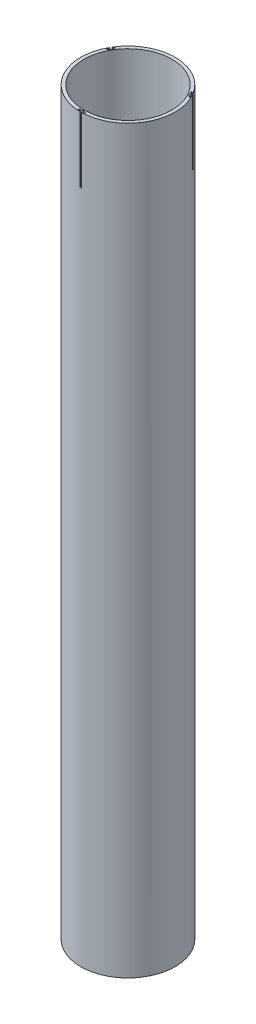
SolidWorks part; units mm, degrees
ref_plane "Front Plane" through (0, 0, 0) normal (0, 0, 1) x (1, 0, 0)
ref_plane "Top Plane" through (0, 0, 0) normal (0, 1, 0) x (1, 0, 0)
ref_plane "Right Plane" through (0, 0, 0) normal (1, 0, 0) x (0, 0, -1)
sketch "Sketch1" plane through (0, 0, 0) normal (0, 1, 0) x (1, 0, 0)
  circle A0 centre (0, 0) radius 57.5
  dimension "D1" = 115
extrude "Boss-Extrude1" add sketch "Sketch1" along normal mid plane 900
ref_plane "Plane1" through (0, 370, 0) normal (0, 1, 0) x (1, 0, 0)
ref_plane "Plane2" through (0, 450, 0) normal (0, 1, 0) x (1, 0, 0)
shell "Shell1" thickness 4 removed face at (0, 450, 57.5) removed face at (0, -450, 57.5)
sketch "Sketch2" plane through (0, 450, 0) normal (0, 1, 0) x (1, 0, 0)
  line L0 (0, 64.7023) -> (0, -68.4384) construction
  line L1 (1, -57.4913) -> (1, -56.5087)
  line L13 (4, -56.5087) -> (4, -55.5087)
  line L14 (1, -56.5087) -> (4, -56.5087)
  line L15 (4, -55.5087) -> (0, -54.5087)
  line L16 (-4, -55.5087) -> (0, -54.5087)
  line L17 (-4, -56.5087) -> (-4, -55.5087)
  line L18 (-1, -56.5087) -> (-4, -56.5087)
  line L19 (-1, -57.4913) -> (-1, -56.5087)
  arc A0 (-1, -57.4913) -> (1, -57.4913) centre (0, 0) ccw
  circle A1 centre (0, 0) radius 57.5 construction
  point P1 (0, 0)
  point P5 (-1, -57.4913)
  point P8 (0, 0)
  point P9 (1, -57.4862)
  point P12 (0, 0)
  point P16 (26.923, -56.7776)
  point P19 (17.4959, -57.4913)
extrude "Cut-Extrude4" cut sketch "Sketch2" against normal blind 80
ref_axis "Axis1" through (0, 0, 0) along (0, 1, 0)
pattern_circular "CirPattern1" count 3 over 360 about axis through (0, 0, 0) along (0, 1, 0) of "Cut-Extrude4"
